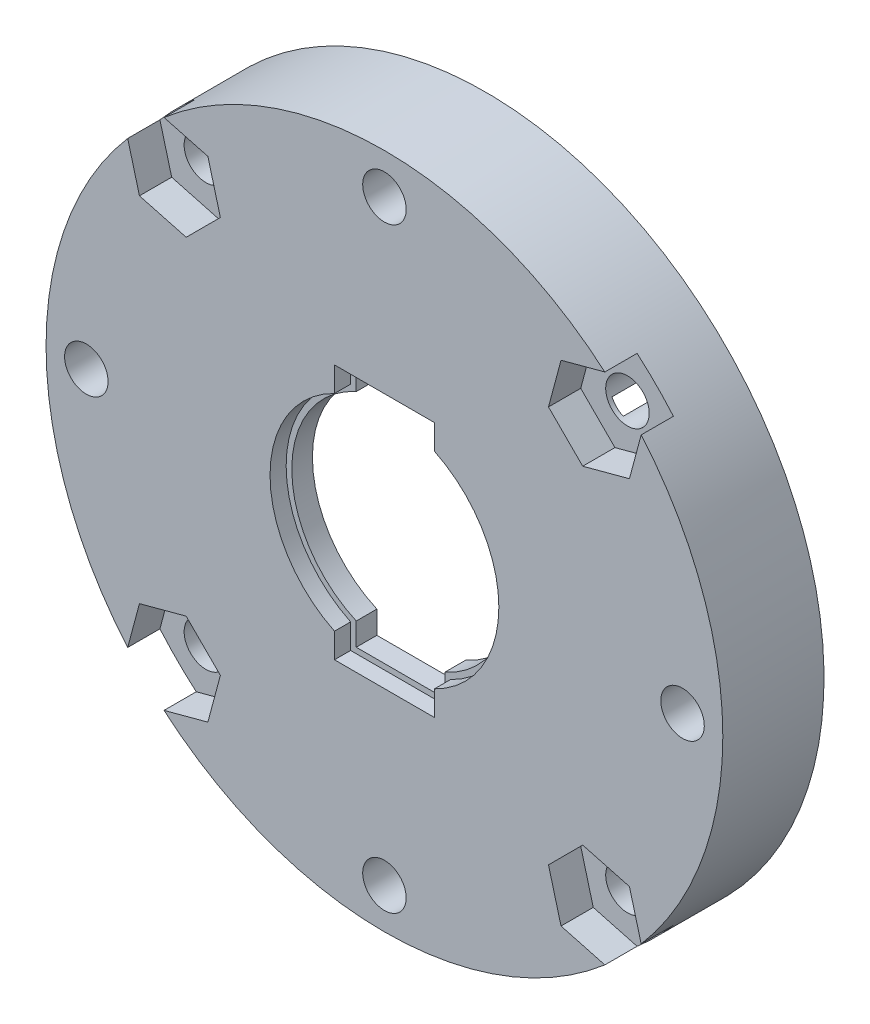
SolidWorks part; units mm, degrees
ref_plane "Front Plane" through (0, 0, 0) normal (0, 0, 1) x (1, 0, 0)
ref_plane "Top Plane" through (0, 0, 0) normal (0, 1, 0) x (1, 0, 0)
ref_plane "Right Plane" through (0, 0, 0) normal (1, 0, 0) x (0, 0, -1)
ref_axis "Z" through (0, 0, -0.1) along (0, 0, 1)
sketch "Sketch3" plane through (0, 0, 0) normal (0, 0, 1) x (1, 0, 0)
  line L0 (-3.1, -6.3875) -> (-3.1, -7.9247)
  line L1 (-3.1, -7.9247) -> (3.1, -7.9247)
  line L2 (3.1, -7.9247) -> (3.1, -6.3875)
  line L3 (3.1, 6.3875) -> (3.1, 7.9244)
  line L4 (3.1, 7.9244) -> (-3.1, 7.9244)
  line L5 (-3.1, 7.9244) -> (-3.1, 6.3875)
  line L132 (3.05, 6.3548) -> (3.05, 6.3561) construction
  line L133 (-3.05, 6.3561) -> (-3.05, 6.3548) construction
  line L134 (3.05, -6.3561) -> (3.05, -6.355) construction
  line L135 (-3.05, -6.355) -> (-3.05, -6.3561) construction
  line L198 (3.05, 6.3548) -> (3.05, 7.8744)
  line L199 (3.05, 7.8744) -> (-3.05, 7.8744)
  line L200 (-3.05, 7.8744) -> (-3.05, 6.3548)
  line L201 (-3.05, 6.3548) -> (-3.4914, 6.1247)
  line L202 (-3.4914, 6.1247) -> (-3.9416, 5.8451)
  line L203 (-3.9416, 5.8451) -> (-4.3696, 5.5325)
  line L204 (-4.3696, 5.5325) -> (-4.7729, 5.1886)
  line L205 (-4.7729, 5.1886) -> (-5.1492, 4.8154)
  line L206 (-5.1492, 4.8154) -> (-5.4964, 4.4149)
  line L207 (-5.4964, 4.4149) -> (-5.8125, 3.9896)
  line L208 (-5.8125, 3.9896) -> (-6.0958, 3.5417)
  line L209 (-6.0958, 3.5417) -> (-6.3446, 3.0737)
  line L210 (-6.3446, 3.0737) -> (-6.5576, 2.5884)
  line L211 (-6.5576, 2.5884) -> (-6.7335, 2.0885)
  line L212 (-6.7335, 2.0885) -> (-6.8714, 1.5768)
  line L213 (-6.8714, 1.5768) -> (-6.9705, 1.0561)
  line L214 (-6.9705, 1.0561) -> (-7.0301, 0.5295)
  line L215 (-7.0301, 0.5295) -> (-7.05, -0.0001)
  line L216 (-7.05, -0.0001) -> (-7.0301, -0.5297)
  line L217 (-7.0301, -0.5297) -> (-6.9705, -1.0563)
  line L218 (-6.9705, -1.0563) -> (-6.8714, -1.577)
  line L219 (-6.8714, -1.577) -> (-6.7335, -2.0887)
  line L220 (-6.7335, -2.0887) -> (-6.5576, -2.5887)
  line L221 (-6.5576, -2.5887) -> (-6.3446, -3.074)
  line L222 (-6.3446, -3.074) -> (-6.0958, -3.5419)
  line L223 (-6.0958, -3.5419) -> (-5.8125, -3.9898)
  line L224 (-5.8125, -3.9898) -> (-5.4964, -4.4152)
  line L225 (-5.4964, -4.4152) -> (-5.1492, -4.8156)
  line L226 (-5.1492, -4.8156) -> (-4.7729, -5.1888)
  line L227 (-4.7729, -5.1888) -> (-4.3696, -5.5327)
  line L228 (-4.3696, -5.5327) -> (-3.9416, -5.8453)
  line L229 (-3.9416, -5.8453) -> (-3.4914, -6.1249)
  line L230 (-3.4914, -6.1249) -> (-3.05, -6.355)
  line L231 (-3.05, -6.355) -> (-3.05, -7.8747)
  line L232 (-3.05, -7.8747) -> (3.05, -7.8747)
  line L233 (3.05, -7.8747) -> (3.05, -6.355)
  line L234 (3.05, -6.355) -> (3.4914, -6.1249)
  line L235 (3.4914, -6.1249) -> (3.9417, -5.8453)
  line L236 (3.9417, -5.8453) -> (4.3696, -5.5327)
  line L237 (4.3696, -5.5327) -> (4.7729, -5.1888)
  line L238 (4.7729, -5.1888) -> (5.1492, -4.8156)
  line L239 (5.1492, -4.8156) -> (5.4964, -4.4152)
  line L240 (5.4964, -4.4152) -> (5.8125, -3.9898)
  line L241 (5.8125, -3.9898) -> (6.0958, -3.5419)
  line L242 (6.0958, -3.5419) -> (6.3447, -3.074)
  line L243 (6.3447, -3.074) -> (6.5576, -2.5887)
  line L244 (6.5576, -2.5887) -> (6.7336, -2.0887)
  line L245 (6.7336, -2.0887) -> (6.8714, -1.577)
  line L246 (6.8714, -1.577) -> (6.9705, -1.0563)
  line L247 (6.9705, -1.0563) -> (7.0301, -0.5297)
  line L248 (7.0301, -0.5297) -> (7.05, -0.0001)
  line L249 (7.05, -0.0001) -> (7.0301, 0.5295)
  line L250 (7.0301, 0.5295) -> (6.9705, 1.0561)
  line L251 (6.9705, 1.0561) -> (6.8714, 1.5768)
  line L252 (6.8714, 1.5768) -> (6.7336, 2.0885)
  line L253 (6.7336, 2.0885) -> (6.5576, 2.5884)
  line L254 (6.5576, 2.5884) -> (6.3447, 3.0737)
  line L255 (6.3447, 3.0737) -> (6.0958, 3.5417)
  line L256 (6.0958, 3.5417) -> (5.8125, 3.9896)
  line L257 (5.8125, 3.9896) -> (5.4964, 4.4149)
  line L258 (5.4964, 4.4149) -> (5.1492, 4.8154)
  line L259 (5.1492, 4.8154) -> (4.7729, 5.1886)
  line L260 (4.7729, 5.1886) -> (4.3696, 5.5325)
  line L261 (4.3696, 5.5325) -> (3.9417, 5.8451)
  line L262 (3.9417, 5.8451) -> (3.4914, 6.1247)
  line L263 (3.4914, 6.1247) -> (3.05, 6.3548)
  line L264 (3.05, 6.3561) -> (3.05, 7.8744) construction
  line L265 (3.05, 7.8744) -> (-3.05, 7.8744) construction
  line L266 (-3.05, 7.8744) -> (-3.05, 6.3561) construction
  line L297 (-3.05, -6.3561) -> (-3.05, -7.8747) construction
  line L298 (-3.05, -7.8747) -> (3.05, -7.8747) construction
  line L299 (3.05, -7.8747) -> (3.05, -6.3561) construction
  arc A1 (-3.05, 6.3561) -> (-3.05, -6.3561) centre (0, 0) ccw construction
  arc A2 (3.05, 6.3561) -> (-3.05, 6.3561) centre (0, 0) ccw construction
  arc A3 (3.05, -6.3561) -> (3.05, 6.3561) centre (0, 0) ccw construction
  arc A4 (-3.05, -6.3561) -> (3.05, -6.3561) centre (0, 0) ccw construction
  circle A5 centre (0, 0) radius 21
  arc A6 (-3.1, 6.3875) -> (-3.1, -6.3875) centre (0, 0) ccw
  arc A7 (3.1, -6.3875) -> (3.1, 6.3875) centre (0, 0) ccw
  dimension "D1" = 14.1
  dimension "D3" = 42
  dimension "D2" = 0.05
  dimension "D4" = 0.05
extrude "Boss-Extrude2" add sketch "Sketch3" against normal blind 1
sketch "Sketch4" plane through (0, 0, -1) normal (0, 0, -1) x (-1, 0, 0)
  line L39 (2.75, 6.1644) -> (2.75, 7.5744)
  line L40 (2.75, 7.5744) -> (-2.75, 7.5744)
  line L41 (-2.75, 7.5744) -> (-2.75, 6.1644)
  line L42 (-2.75, -6.1644) -> (-2.75, -7.5747)
  line L43 (-2.75, -7.5747) -> (2.75, -7.5747)
  line L44 (2.75, -7.5747) -> (2.75, -6.1644)
  circle A14 centre (0, 0) radius 21
  arc A17 (-2.75, 6.1644) -> (-2.75, -6.1644) centre (0, 0) ccw
  arc A18 (2.75, -6.1644) -> (2.75, 6.1644) centre (0, 0) ccw
extrude "Boss-Extrude3" add sketch "Sketch4" along normal blind 5.28
sketch "Sketch5" plane through (0, 0, -6.28) normal (0, 0, -1) x (-1, 0, 0)
  circle A0 centre (0, 0) radius 17.25
  dimension "D1" = 34.5
extrude "Cut-Extrude1" cut sketch "Sketch5" against normal blind 4
sketch "Sketch6" plane through (0, 0, 0) normal (0, 0, 1) x (1, 0, 0)
  line L0 (0, 0) -> (13.0815, 13.0815) construction
  line L1 (-16.3801, 0) -> (0, 0) construction
  line L3 (13.8585, 15.9814) -> (10.9586, 15.2044)
  line L4 (10.9586, 15.2044) -> (10.1816, 12.3044)
  line L5 (10.1816, 12.3044) -> (12.3044, 10.1816)
  line L6 (12.3044, 10.1816) -> (15.2044, 10.9586)
  line L7 (15.2044, 10.9586) -> (15.9814, 13.8585)
  line L8 (15.9814, 13.8585) -> (13.8585, 15.9814)
  circle A0 centre (13.0815, 13.0815) radius 2.6 construction
  dimension "D3" = 5.2
  dimension "D1" = 135
  dimension "D2" = 18.5
extrude "Cut-Extrude2" cut sketch "Sketch6" against normal blind 2
sketch "Sketch8" plane through (0, 0, 0) normal (0, 0, 1) x (1, 0, 0)
  line L0 (36.6653, 0) -> (49.0214, 0) construction
  line L1 (0, 0) -> (13.0815, 13.0815) construction
  circle A0 centre (0, 0) radius 18.5 construction
  circle A1 centre (13.0815, 13.0815) radius 1.35
  dimension "D1" = 37
  dimension "D3" = 2.7
  dimension "D2" = 135
extrude "Cut-Extrude4" cut sketch "Sketch8" against normal through all
pattern_circular "CirPattern1" count 4 over 360 about axis through (0, 0, -0.1) along (0, 0, 1) of "Cut-Extrude2", "Cut-Extrude4"
ref_plane "Plane4" through (0, 0, 0) normal (-0.7071, 0.7071, 0) x (0, 0, 1)
pattern_circular "CirPattern2" count 8 over 360 about axis through (0, 0, -0.1) along (0, 0, 1) of "Cut-Extrude4"
